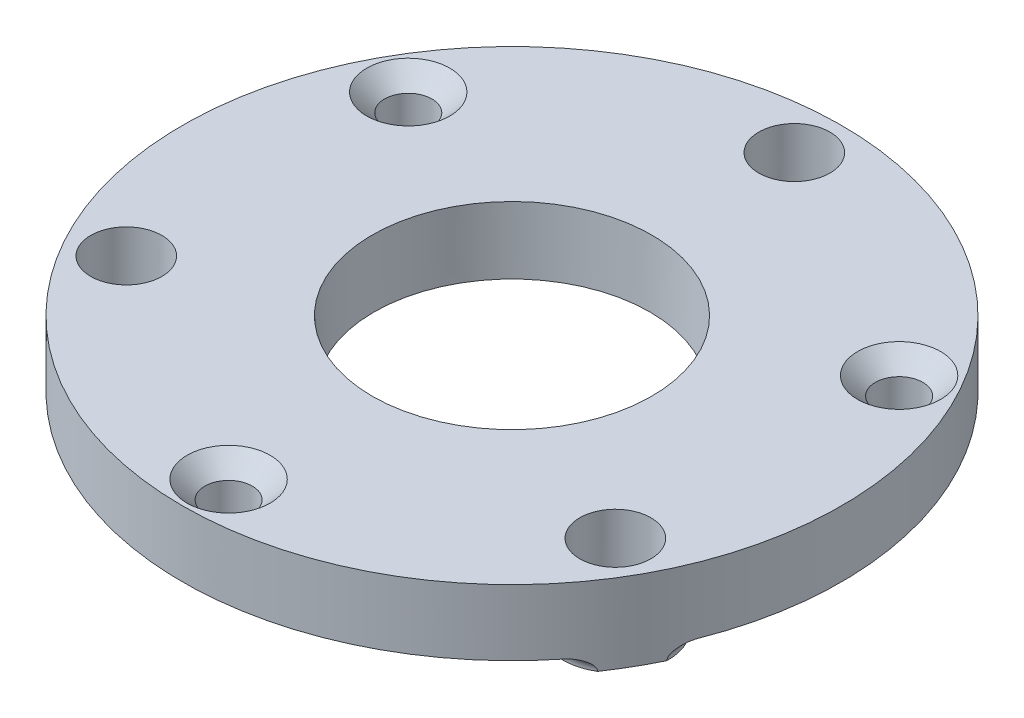
SolidWorks part; units mm, degrees
ref_plane "Alzado" through (0, 0, 0) normal (0, 0, 1) x (1, 0, 0)
ref_plane "Planta" through (0, 0, 0) normal (0, 1, 0) x (1, 0, 0)
ref_plane "Vista lateral" through (0, 0, 0) normal (1, 0, 0) x (0, 0, -1)
sketch "Croquis1" plane through (0, 0, 0) normal (0, 1, 0) x (1, 0, 0)
  circle A0 centre (0, 0) radius 25
  dimension "D1" = 50
extrude "Saliente-Extruir1" add sketch "Croquis1" along normal blind 5
sketch "Croquis2" plane through (0, 5, 0) normal (0, 1, 0) x (1, 0, 0)
  circle A0 centre (0, 0) radius 21.42 construction
  circle A1 centre (0, 21.42) radius 2.7
  circle A2 centre (18.5503, -10.71) radius 2.7
  circle A3 centre (-18.5503, -10.71) radius 2.7
  dimension "D1" = 42.84
  dimension "D2" = 5.4
  dimension "D3" = 3
extrude "Cortar-Extruir2" cut sketch "Croquis2" against normal blind 5
sketch "Croquis3" plane through (0, 5, 0) normal (0, 1, 0) x (1, 0, 0)
  circle A0 centre (0, 0) radius 21.5 construction
  circle A1 centre (0, -21.5) radius 1.45
  circle A2 centre (-18.6195, 10.75) radius 1.45
  circle A3 centre (18.6195, 10.75) radius 1.45
  dimension "D1" = 43
  dimension "D2" = 2.9
  dimension "D3" = 3
extrude "Cortar-Extruir3" cut sketch "Croquis3" against normal blind 5
sketch "Croquis4" plane through (0, 5, 0) normal (0, 1, 0) x (1, 0, 0)
  circle A0 centre (0, 0) radius 10.6
  dimension "D1" = 21.2
extrude "Cortar-Extruir4" cut sketch "Croquis4" against normal blind 5 draft 1.5
hole_wizard "Avellanado para tornillo con cabeza plana de M31" positions "Croquis5" profile "Croquis6" countersink size "M3" standard "Ansi Metric" end condition through all
sketch "Croquis5" plane through (0, 5, 0) normal (0, 1, 0) x (1, 0, 0)
  point P0 (-18.6195, 10.75)
  point P3 (18.6195, 10.75)
  point P6 (0, -21.5)
sketch "Croquis6" plane through (-18.6195, 5, -10.75) normal (1, 0, 0) x (0, 0, 1)
  line L0 (0, 0) -> (0, 5)
  line L1 (0, 5) -> (1.8, 5)
  line L2 (1.8, 5) -> (1.8, 1.35)
  line L3 (1.8, 1.35) -> (3.15, 0)
  line L5 (3.15, 0) -> (0, 0)
  line L6 (-1.8, 1.35) -> (-3.15, 0) construction
  line L11 (0, -6.35) -> (0, 107.95) construction
  dimension "Diámetro de taladro hasta el siguiente" = 3.6
  dimension "Profundidad de taladro hasta el siguiente" = 5
  dimension "Diámetro de avellanado cercano" = 6.3
  dimension "Ángulo de avellanado cercano" = 90
sketch "Croquis7" plane through (0, 0, 0) normal (0, -1, 0) x (-1, 0, 0)
  arc A0 (22.5494, -10.7947) -> (20.6232, -14.131) centre (18.5503, -10.71) ccw
  arc A1 (-20.6232, -14.131) -> (-22.5494, -10.7947) centre (-18.5503, -10.71) ccw
  arc A2 (-1.9262, 24.9257) -> (1.9262, 24.9257) centre (0, 21.42) ccw
  arc A3 (20.6232, -14.131) -> (22.5494, -10.7947) centre (0, 0) ccw
  arc A4 (1.9262, 24.9257) -> (-1.9262, 24.9257) centre (0, 0) ccw
  arc A5 (-22.5494, -10.7947) -> (-20.6232, -14.131) centre (0, 0) ccw
  circle A6 centre (18.5503, -10.71) radius 2.7
  circle A7 centre (-18.5503, -10.71) radius 2.7
  circle A8 centre (0, 21.42) radius 2.7
  dimension "D1" = 8
extrude "Saliente-Extruir2" add sketch "Croquis7" along normal blind 1
fillet "Redondeo1" radius 1 3 edges at (0, 0, -17.42) (15.0862, 0, 8.71) (-15.0862, 0, 8.71)
